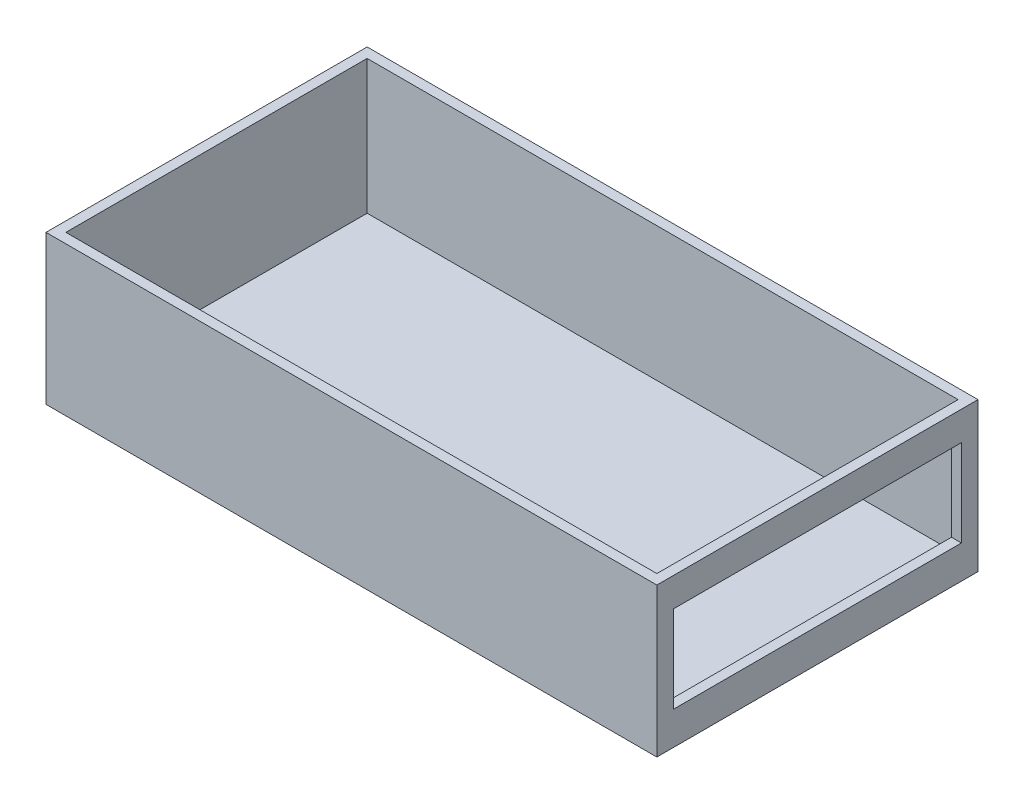
SolidWorks part; units mm, degrees
ref_plane "Front" through (0, 0, 0) normal (0, 0, 1) x (1, 0, 0)
ref_plane "Top" through (0, 0, 0) normal (0, 1, 0) x (1, 0, 0)
ref_plane "Right" through (0, 0, 0) normal (1, 0, 0) x (0, 0, -1)
sketch "Sketch1" plane through (0, 0, 0) normal (0, 1, 0) x (1, 0, 0)
  line L1 (35, -17.5) -> (-35, -17.5) construction
  line L2 (35, -17.5) -> (35, 17.5) construction
  line L3 (35, 17.5) -> (-35, 17.5) construction
  line L4 (-35, -17.5) -> (-35, 17.5) construction
  line L5 (35, -17.5) -> (-35, 17.5) construction
  line L6 (35, 17.5) -> (-35, -17.5) construction
  line L7 (35.7, -18.2) -> (-35.7, -18.2)
  line L8 (35.7, -18.2) -> (35.7, 18.2)
  line L9 (35.7, 18.2) -> (-35.7, 18.2)
  line L10 (-35.7, -18.2) -> (-35.7, 18.2)
  line L11 (35.7, -18.2) -> (-35.7, 18.2) construction
  line L12 (35.7, 18.2) -> (-35.7, -18.2) construction
  line L13 (36.9, -19.4) -> (-36.9, -19.4)
  line L14 (36.9, -19.4) -> (36.9, 19.4)
  line L15 (36.9, 19.4) -> (-36.9, 19.4)
  line L16 (-36.9, -19.4) -> (-36.9, 19.4)
  line L17 (36.9, -19.4) -> (-36.9, 19.4) construction
  line L18 (36.9, 19.4) -> (-36.9, -19.4) construction
  point P0 (0, 0)
  point P6 (0, 0)
  point P11 (0, 0)
  dimension "D1" = 70
  dimension "D2" = 35
  dimension "D3" = 0.7
  dimension "D4" = 0.7
  dimension "D5" = 1.2
  dimension "D6" = 1.2
extrude "Boss-Extrude1" add sketch "Sketch1" along normal blind 1.8 contours L10 L7 L8 L9 | L16 L13 L14 L15 L7 L10 L9 L8 region at (0, 0, 0) region at (0, 0, 18.5662)
extrude "Boss-Extrude2" add sketch "Sketch1<3>" along normal blind 18
sketch "Sketch1<3>" plane through (0, 0, 0) normal (0, 1, 0) x (1, 0, 0) same geometry as "Sketch1"
sketch "Sketch2" plane through (36.9, 0, 0) normal (1, 0, 0) x (0, 0, -1)
  line L0 (-19.4, 18) -> (-19.4, 0) construction
  line L1 (17.4, 4) -> (-17.4, 4)
  line L2 (17.4, 4) -> (17.4, 14.5)
  line L3 (17.4, 14.5) -> (-17.4, 14.5)
  line L4 (-17.4, 4) -> (-17.4, 14.5)
  line L5 (17.4, 4) -> (-17.4, 14.5) construction
  line L6 (17.4, 14.5) -> (-17.4, 4) construction
  line L7 (-19.4, 18) -> (19.4, 18) construction
  line L8 (-19.4, 0) -> (19.4, 0) construction
  point P0 (0, 9.25)
  point P7 (0, 0)
  dimension "D1" = 2
  dimension "D2" = 3.5
  dimension "D3" = 4
extrude "Cut-Extrude1" cut sketch "Sketch2" against normal up to surface (1.2 mm away) up to face at (35.7, 9.9, 0)
